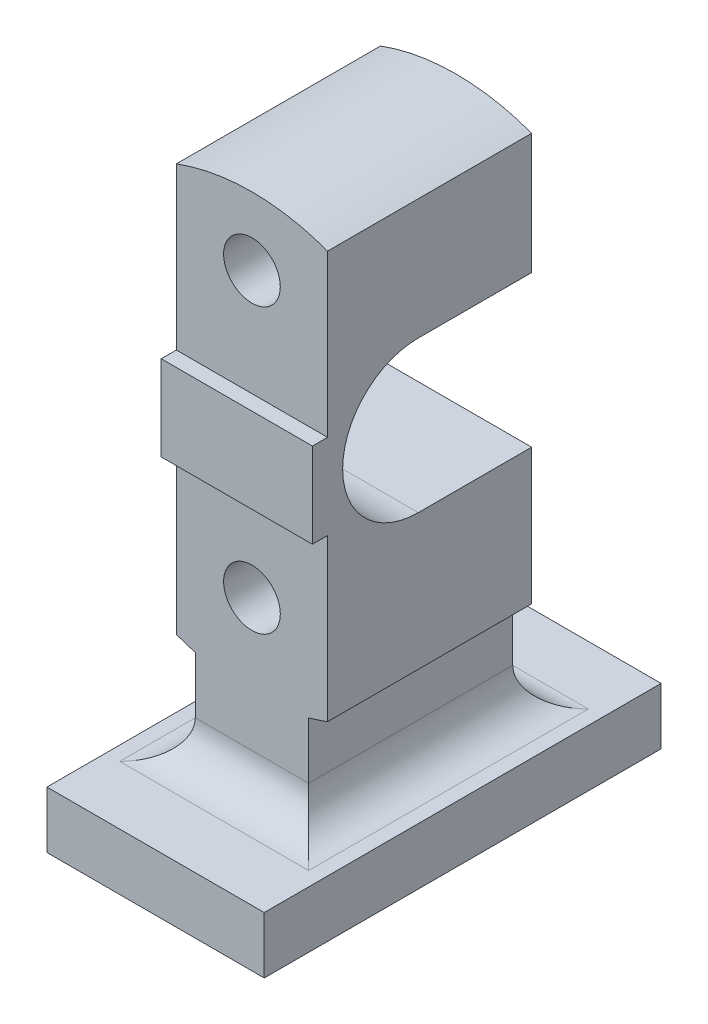
SolidWorks part; units mm, degrees
ref_plane "Front Plane" through (0, 0, 0) normal (0, 0, 1) x (1, 0, 0)
ref_plane "Top Plane" through (0, 0, 0) normal (0, 1, 0) x (1, 0, 0)
ref_plane "Right Plane" through (0, 0, 0) normal (1, 0, 0) x (0, 0, -1)
sketch "Sketch3" plane through (0, 0, 0) normal (0, 0, 1) x (1, 0, 0)
  line L0 (-40, 22.5) -> (-40, 107.8193)
  line L1 (-40, 22.5) -> (40, 22.5)
  line L2 (-40, 22.5) -> (-40, -22.5)
  line L3 (-40, -22.5) -> (40, -22.5)
  line L4 (40, 22.5) -> (40, -22.5)
  line L5 (40, 22.5) -> (40, 107.8193)
  line L6 (40, -22.5) -> (40, -107.8193)
  line L7 (-40, -22.5) -> (-40, -107.8193)
  line L8 (0, 0) -> (0, -193.3516) construction
  line L9 (30, -161.018) -> (57.5, -161.018)
  line L11 (-30, -111.018) -> (-30, -161.018)
  line L13 (30, -111.018) -> (30, -161.018)
  line L14 (57.5, -161.018) -> (57.5, -191.018)
  line L15 (57.5, -191.018) -> (-57.5, -191.018)
  line L16 (-57.5, -191.018) -> (-57.5, -161.018)
  line L17 (-57.5, -161.018) -> (-30, -161.018)
  line L18 (-30, -161.018) -> (30, -161.018)
  arc A0 (-40, -107.8193) -> (-30, -111.018) centre (0, 0) ccw
  arc A1 (40, 107.8193) -> (-40, 107.8193) centre (0, 0) ccw
  arc A2 (30, -111.018) -> (40, -107.8193) centre (0, 0) ccw
  dimension "D5" = 230
  dimension "D1" = 45
  dimension "D2" = 80
  dimension "D3" = 22.5
  dimension "D4" = 40
  dimension "D6" = 30
  dimension "D7" = 30
  dimension "D8" = 50
  dimension "D9" = 115
  dimension "D10" = 30
  dimension "D11" = 57.5
extrude "Boss-Extrude2" add sketch "Sketch3" along normal mid plane 210 contours L18 L8 L15 L14 L9 | L8 L18 L17 L16 L15 region at (28.75, -176.018, 0) region at (-28.75, -176.018, 0)
extrude "Boss-Extrude3" add sketch "Sketch3<3>" along normal mid plane 108 contours L8 L3 L7 A0 L11 L18 | L3 L8 L18 L13 A2 L6 | L4 L1 L2 L3 | L5 A1 L0 L1 region at (0, 67.5938, 0) region at (0, 21.5821, 0) region at (-18.4571, -87.3007, 0) region at (18.4571, -87.3007, 0)
sketch "Sketch3<3>" plane through (0, 0, 0) normal (0, 0, 1) x (1, 0, 0) same geometry as "Sketch3"
extrude "Boss-Extrude4" add sketch "Sketch3<4>" along normal blind 62 contours L4 L1 L2 L3 region at (0, 0, 0)
sketch "Sketch3<4>" plane through (0, 0, 0) normal (0, 0, 1) x (1, 0, 0) same geometry as "Sketch3"
sketch "Sketch5" plane through (40, 0, 0) normal (1, 0, 0) x (0, 0, -1)
  line L0 (-105, -191.018) -> (105, -191.018) construction
  line L1 (54, 107.8193) -> (54, -107.8193) construction
  line L2 (-6, 43.982) -> (54, 43.982)
  line L3 (-6, -36.018) -> (54, -36.018)
  arc A0 (-6, 43.982) -> (-6, -36.018) centre (-6, 3.982) ccw
  dimension "D1" = 80
  dimension "D2" = 60
  dimension "D3" = 195
extrude "Cut-Extrude1" cut sketch "Sketch5" against normal through all and the other way through all
fillet "Fillet1" radius 20 4 edges at (0, -161.018, 54) (30, -161.018, 0) (0, -161.018, -54) (-30, -161.018, 0)
sketch "Sketch7" plane through (0, 0, 54) normal (0, 0, 1) x (1, 0, 0)
  line L0 (-57.5, -161.018) -> (57.5, -161.018) construction
  circle A0 centre (0, -71.018) radius 15
  circle A1 centre (0, 78.982) radius 15
  dimension "D1" = 30
  dimension "D2" = 150
  dimension "D3" = 90
extrude "Cut-Extrude2" cut sketch "Sketch7" against normal through all
